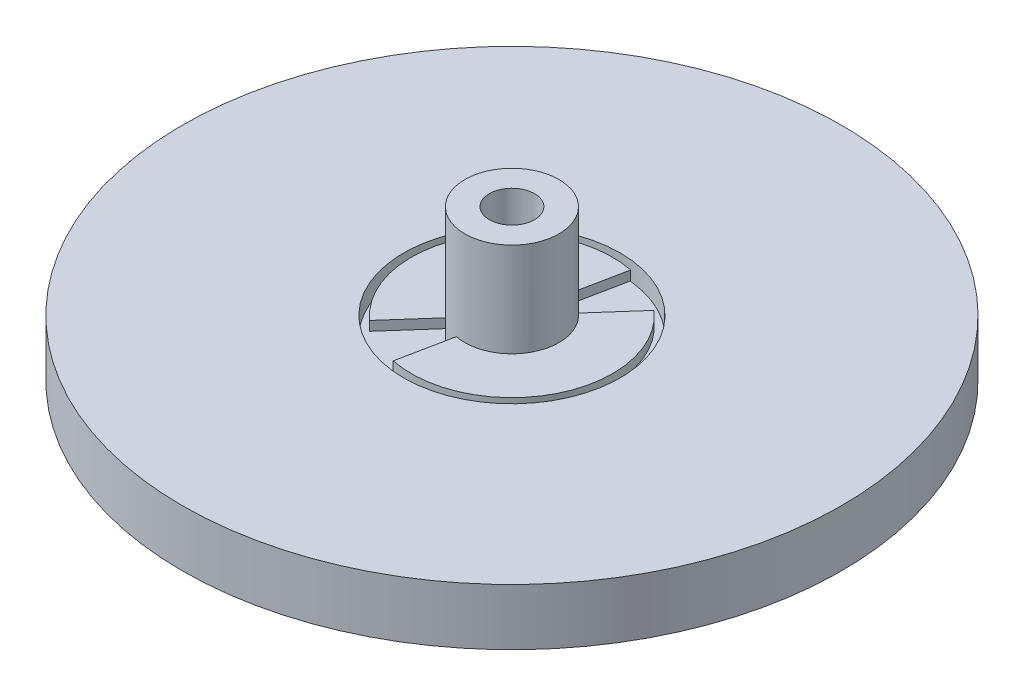
SolidWorks part; units mm, degrees
ref_plane "Front Plane" through (0, 0, 0) normal (0, 0, 1) x (1, 0, 0)
ref_plane "Top Plane" through (0, 0, 0) normal (0, 1, 0) x (1, 0, 0)
ref_plane "Right Plane" through (0, 0, 0) normal (1, 0, 0) x (0, 0, -1)
sketch "Sketch1" plane through (0, 0, 0) normal (0, 1, 0) x (1, 0, 0)
  circle A0 centre (0, 0) radius 175
extrude "Boss-Extrude1" add sketch "Sketch1" along normal blind 30
sketch "Sketch2" plane through (0, 30, 0) normal (0, 1, 0) x (1, 0, 0)
  circle A0 centre (0, 0) radius 25
  circle A1 centre (0, 0) radius 12
extrude "Boss-Extrude2" add sketch "Sketch2" along normal blind 50 and the other way blind 15
sketch "Sketch3" plane through (0, 30, 0) normal (0, 1, 0) x (1, 0, 0)
  circle A0 centre (0, 0) radius 57.5
extrude "Cut-Extrude1" cut sketch "Sketch3" against normal blind 10
sketch "Sketch5" plane through (0, 30, 0) normal (0, -1, 0) x (1, 0, 0)
  circle A0 centre (0, 0) radius 53.5
extrude "Boss-Extrude3" add sketch "Sketch5" along normal blind 5
sketch "Sketch6" plane through (0, 30, 0) normal (0, 1, 0) x (1, 0, 0)
  circle A1 centre (0, 0) radius 25
extrude "Boss-Extrude4" add sketch "Sketch6" against normal blind 15
sketch "Sketch7" plane through (0, 30, 0) normal (0, 1, 0) x (1, 0, 0)
  line L0 (4.9788, 24.4992) -> (10.6319, 52.4329)
  line L1 (-16.5614, -18.7275) -> (-35.4414, -40.0769)
  line L2 (-4.9788, -24.4992) -> (-10.6319, -52.4329)
  line L3 (16.5614, 18.7275) -> (35.4414, 40.0769)
  arc A0 (-10.6319, -52.4329) -> (-35.4414, -40.0769) centre (0, 0) cw
  circle A1 centre (0, 0) radius 53.5 construction
  arc A2 (10.6319, 52.4329) -> (35.4414, 40.0769) centre (0, 0) cw
  arc A3 (-16.5614, -18.7275) -> (-4.9788, -24.4992) centre (0, 0) ccw
  arc A4 (16.5614, 18.7275) -> (4.9788, 24.4992) centre (0, 0) ccw
  dimension "D1" = 2
extrude "Cut-Extrude3" cut sketch "Sketch7" against normal blind 10
